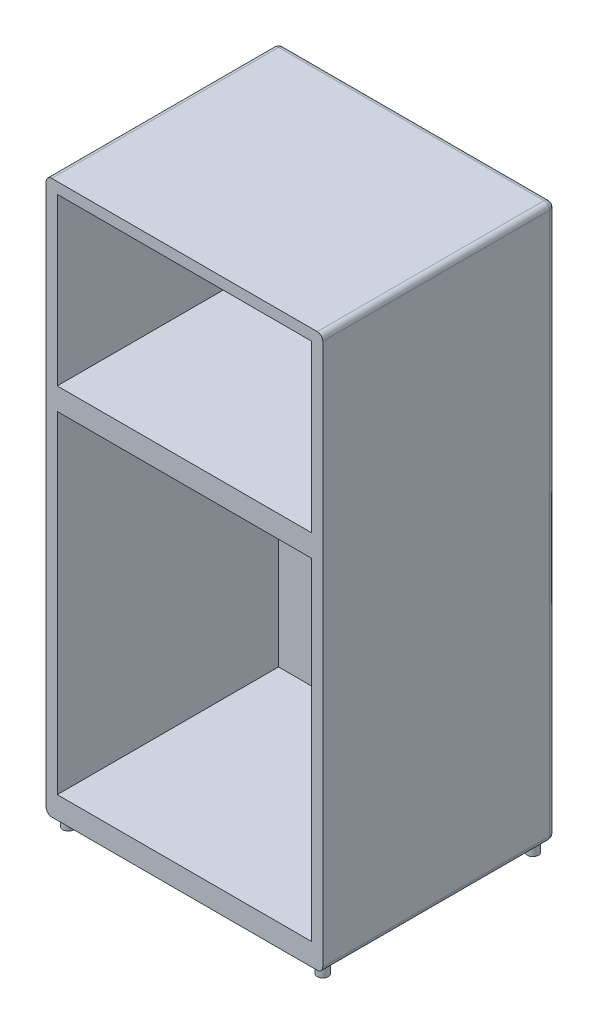
SolidWorks part; units mm, degrees
ref_plane "前基準面" through (0, 0, 0) normal (0, 0, 1) x (1, 0, 0)
ref_plane "上基準面" through (0, 0, 0) normal (0, 1, 0) x (1, 0, 0)
ref_plane "右基準面" through (0, 0, 0) normal (1, 0, 0) x (0, 0, -1)
sketch "草圖1" plane through (0, 0, 0) normal (0, 0, 1) x (1, 0, 0)
  line L1 (-12.5, 25) -> (12.5, 25)
  line L2 (-12.5, 25) -> (-12.5, -25)
  line L3 (-12.5, -25) -> (12.5, -25)
  line L4 (12.5, 25) -> (12.5, -25)
  line L5 (-12.5, 25) -> (12.5, -25) construction
  line L6 (-12.5, -25) -> (12.5, 25) construction
  point P0 (0, 0)
  dimension "D1" = 50
  dimension "D2" = 25
extrude "填料-伸長1" add sketch "草圖1" along normal blind 21
sketch "草圖2" plane through (0, 0, 21) normal (0, 0, 1) x (1, 0, 0)
  line L0 (0, -25) -> (0, 25) construction
  line L1 (-12.5, -25) -> (12.5, -25) construction
  line L2 (12.5, 25) -> (-12.5, 25) construction
  line L3 (12.5, -25) -> (12.5, 25) construction
  line L4 (-11.5, 24) -> (11.5, 24)
  line L5 (-11.5, 24) -> (-11.5, 9)
  line L6 (-11.5, 9) -> (11.5, 9)
  line L7 (11.5, 24) -> (11.5, 9)
  line L8 (-11.5, 24) -> (11.5, 9) construction
  line L9 (-11.5, 9) -> (11.5, 24) construction
  line L11 (-11.5, 7) -> (11.5, 7)
  line L12 (-11.5, 7) -> (-11.5, -23)
  line L13 (-11.5, -23) -> (11.5, -23)
  line L14 (11.5, 7) -> (11.5, -23)
  line L15 (-11.5, 7) -> (11.5, -23) construction
  line L16 (-11.5, -23) -> (11.5, 7) construction
  point P6 (0, 16.5)
  point P14 (0, -8)
  dimension "D1" = 15
  dimension "D2" = 1
  dimension "D3" = 1
  dimension "D4" = 2
  dimension "D5" = 1
  dimension "D6" = 2
extrude "除料-伸長1" cut sketch "草圖2" against normal blind 20
sketch "草圖3" plane through (0, -25, 0) normal (0, -1, 0) x (1, 0, 0)
  line L8 (-11.5, 1) -> (11.5, 1)
  line L9 (11.5, 1) -> (11.5, 20)
  line L10 (11.5, 20) -> (-11.5, 20)
  line L11 (-11.5, 20) -> (-11.5, 1)
  line L12 (-11.5, 1) -> (11.5, 1) construction
  line L13 (11.5, 1) -> (11.5, 20) construction
  line L14 (11.5, 20) -> (-11.5, 20) construction
  line L15 (-11.5, 20) -> (-11.5, 1) construction
  circle A0 centre (-11.5, 20) radius 0.5
  circle A1 centre (11.5, 20) radius 0.5
  circle A2 centre (11.5, 1) radius 0.5
  circle A3 centre (-11.5, 1) radius 0.5
  dimension "D2" = 1
  dimension "D1" = 1
extrude "填料-伸長2" add sketch "草圖3" along normal blind 1
fillet "圓角1" radius 0.5 8 edges at (0, 25, 0) (-12.5, 0, 0) (0, -25, 0) (12.5, 0, 0) (12.5, -25, 10.5) (-12.5, -25, 10.5) (12.5, 25, 10.5) (-12.5, 25, 10.5)
